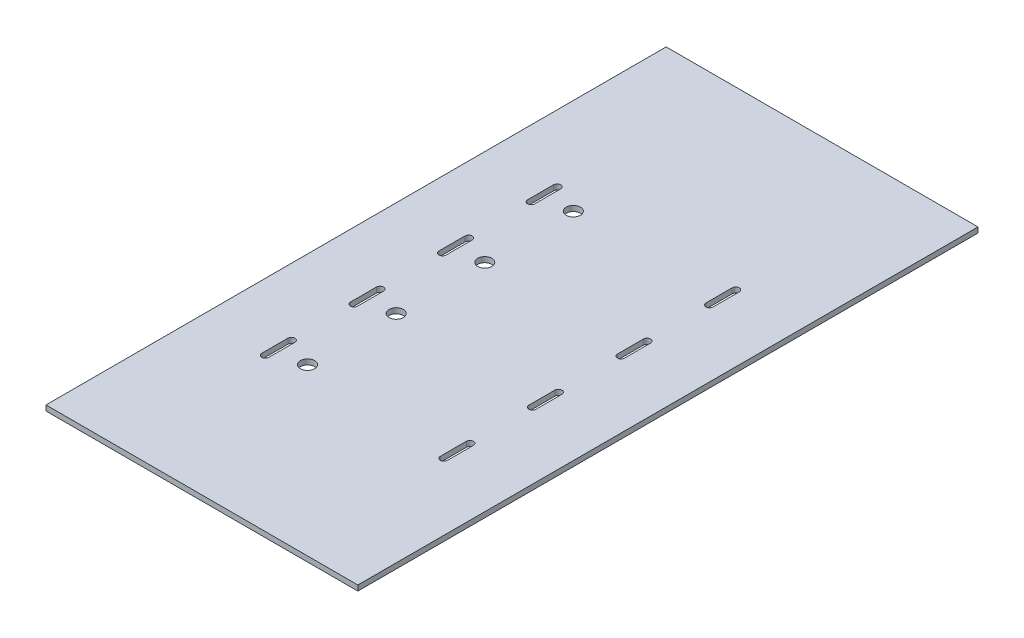
SolidWorks part; units mm, degrees
ref_plane "Front Plane" through (0, 0, 0) normal (0, 0, 1) x (1, 0, 0)
ref_plane "Top Plane" through (0, 0, 0) normal (0, 1, 0) x (1, 0, 0)
ref_plane "Right Plane" through (0, 0, 0) normal (1, 0, 0) x (0, 0, -1)
sketch "Sketch1" plane through (0, 0, 0) normal (0, 1, 0) x (1, 0, 0)
  line L1 (0, 0) -> (176, 0)
  line L2 (0, 0) -> (0, 350)
  line L3 (0, 350) -> (176, 350)
  line L4 (176, 0) -> (176, 350)
  dimension "D1" = 350
  dimension "D2" = 176
extrude "Boss-Extrude1" add sketch "Sketch1" along normal blind 3
sketch "Sketch2" plane through (0, 3, 0) normal (0, 1, 0) x (1, 0, 0)
  line L0 (176, 0) -> (176, 70)
  line L1 (176, 0) -> (176, 350) construction
  line L2 (176, 70) -> (88, 70)
  line L3 (176, 70) -> (176, 120)
  line L4 (176, 120) -> (176, 170)
  line L5 (176, 170) -> (176, 220)
  line L6 (176, 120) -> (88, 120)
  line L7 (176, 170) -> (88, 170)
  line L8 (176, 220) -> (88, 220)
  line L9 (88, 70) -> (88, 93.5)
  line L10 (88, 120) -> (88, 143.5)
  line L11 (88, 170) -> (88, 193.5)
  line L12 (88, 220) -> (88, 243.5)
hole_wizard "Ø4.0mm Dowel Slot1" positions "Sketch6" profile "Sketch7" size "Ø4.0" standard "ANSI Metric" slot yes end condition up to next
sketch "Sketch6" plane through (0, 0, 0) normal (0, -1, 0) x (-1, 0, 0)
  line L0 (-138.375, 84.15) -> (-138.375, 102.85) construction
  point P0 (-138.375, 93.5)
  point P7 (-37.625, 93.5)
  point P10 (-138.375, 143.5)
  point P13 (-37.625, 143.5)
  point P16 (-138.375, 193.5)
  point P19 (-37.625, 193.5)
  point P22 (-138.375, 243.5)
  point P25 (-37.625, 243.5)
  point P27 (0, 0)
  point P28 (-138.375, 193.5)
  point P30 (-66, 193.5)
  point P31 (-37.625, 193.5)
  point P33 (0, 0)
  point P34 (-138.375, 243.5)
  point P36 (0, 0)
  point P37 (-37.625, 243.5)
  point P38 (0, 0)
  point P39 (-37.625, 243.5)
  point P41 (0, 0)
  point P42 (0, 0)
  point P43 (-138.375, 143.5)
  point P45 (-66, 143.5)
  point P46 (-37.625, 143.5)
  point P48 (0, 0)
  point P49 (-110, 93.5)
  point P50 (-138.375, 93.5)
  point P52 (-66, 93.5)
  point P53 (-37.625, 93.5)
  dimension "D1" = 18.7
sketch "Sketch7" plane through (138.375, 0, -93.5) normal (1, 0, 0) x (0, 0, -1)
  line L0 (0, 0) -> (0, 3)
  line L1 (0, 3) -> (2, 3)
  line L2 (2, 3) -> (2, 0)
  line L5 (2, 0) -> (0, 0)
  line L11 (0, -6.35) -> (0, 107.95) construction
  dimension "Thru Hole Dia." = 4
  dimension "Thru Hole Depth" = 3
hole_wizard "Ø8.0mm Dowel Hole1" positions "Sketch8" profile "Sketch9" hole size "Ø8.0" standard "AS" end condition up to next
sketch "Sketch8" plane through (0, 3, 0) normal (0, 1, 0) x (1, 0, 0)
  point P0 (54.125, 93.5)
  point P3 (54.125, 143.5)
  point P6 (54.125, 193.5)
  point P9 (54.125, 243.5)
sketch "Sketch9" plane through (54.125, 3, -93.5) normal (1, 0, 0) x (0, 0, 1)
  line L0 (0, 0) -> (0, 3)
  line L1 (0, 3) -> (4, 3)
  line L2 (4, 3) -> (4, 0)
  line L5 (4, 0) -> (0, 0)
  line L11 (0, -6.35) -> (0, 107.95) construction
  dimension "Thru Hole Dia." = 8
  dimension "Thru Hole Depth" = 3
sketch "Sketch11" plane through (0, 0, 0) normal (0, -1, 0) x (-1, 0, 0)
  line L0 (-176, 350) -> (-176, 300)
  line L1 (-176, 0) -> (-176, 350) construction
  line L2 (-176, 300) -> (-88, 300)
sketch "Sketch14" plane through (0, 0, 0) normal (0, -1, 0) x (1, 0, 0)
  line L0 (49.9068, -300.32) -> (52.4947, -304.0511)
  line L1 (52.4947, -304.0511) -> (49.9068, -307.782)
  line L2 (49.9068, -307.782) -> (47.319, -311.513)
  line L3 (47.319, -311.513) -> (42.4156, -311.514)
  line L4 (42.4156, -311.514) -> (37.5122, -311.515)
  line L5 (37.5122, -311.515) -> (37.5122, -312.2245)
  line L6 (37.5122, -312.2245) -> (37.5122, -312.934)
  line L7 (37.5122, -312.934) -> (37.6262, -313.007)
  line L8 (36.814, -313.0151) -> (36.9178, -312.9503)
  line L9 (36.9178, -312.9503) -> (36.9187, -312.2086)
  line L10 (36.9187, -312.2086) -> (36.9195, -311.4669)
  line L11 (36.9195, -311.4669) -> (34.3456, -307.759)
  line L12 (34.3456, -307.759) -> (31.7716, -304.0511)
  line L13 (31.7716, -304.0511) -> (34.3595, -300.3201)
  line L14 (34.3595, -300.3201) -> (36.9473, -296.5891)
  line L15 (36.9473, -296.5891) -> (42.1332, -296.5891)
  line L16 (42.1332, -296.5891) -> (47.319, -296.5891)
  line L17 (47.319, -296.5891) -> (49.9068, -300.32)
  line L18 (35.9721, -306.857) -> (37.9137, -309.6536)
  line L19 (37.9137, -309.6536) -> (42.1332, -309.6536)
  line L20 (42.1332, -309.6536) -> (46.3526, -309.6536)
  line L21 (46.3526, -309.6536) -> (48.2943, -306.857)
  line L22 (46.5096, -298.6753) -> (46.3442, -298.4392)
  line L23 (46.3442, -298.4392) -> (42.129, -298.4438)
  line L24 (42.129, -298.4438) -> (37.9137, -298.4485)
  line L25 (37.9137, -298.4485) -> (35.9721, -301.2451)
  line L26 (151.2751, -299.3328) -> (144.2407, -299.3375)
  line L27 (144.2407, -299.3375) -> (143.662, -300.0043)
  line L28 (143.662, -300.0043) -> (143.0832, -300.671)
  line L29 (143.0832, -300.671) -> (143.0825, -302.0323)
  line L30 (143.0825, -302.0323) -> (143.0818, -303.3936)
  line L31 (143.0818, -303.3936) -> (143.6694, -304.074)
  line L32 (143.6694, -304.074) -> (144.257, -304.7544)
  line L33 (144.257, -304.7544) -> (149.8247, -304.7546)
  line L34 (149.8247, -304.7546) -> (155.3924, -304.7548)
  line L35 (155.3924, -304.7548) -> (156.858, -306.452)
  line L36 (156.858, -306.452) -> (158.3236, -308.1492)
  line L37 (158.3236, -308.1492) -> (158.3236, -310.1795)
  line L38 (158.3236, -310.1795) -> (158.3236, -312.2098)
  line L39 (158.3236, -312.2098) -> (156.8568, -313.9089)
  line L40 (156.8568, -313.9089) -> (155.3901, -315.6081)
  line L41 (155.3901, -315.6081) -> (148.6478, -315.6035)
  line L42 (148.6478, -315.6035) -> (141.9056, -315.5988)
  line L43 (141.9056, -315.5988) -> (141.3264, -314.2576)
  line L44 (147.7806, -312.8848) -> (154.8139, -312.8841)
  line L45 (154.8139, -312.8841) -> (155.3923, -312.2134)
  line L46 (155.3923, -312.2134) -> (155.9707, -311.5427)
  line L47 (155.9707, -311.5427) -> (155.9711, -310.1814)
  line L48 (155.9711, -310.1814) -> (155.9715, -308.82)
  line L49 (155.9715, -308.82) -> (155.3846, -308.1395)
  line L50 (155.3846, -308.1395) -> (154.7977, -307.4589)
  line L51 (154.7977, -307.4589) -> (149.23, -307.4589)
  line L52 (149.23, -307.4589) -> (143.6624, -307.4589)
  line L53 (143.6624, -307.4589) -> (142.1956, -305.7597)
  line L54 (142.1956, -305.7597) -> (140.7288, -304.0604)
  line L55 (140.7288, -304.0604) -> (140.7288, -302.0378)
  line L56 (140.7288, -302.0378) -> (140.7288, -300.0151)
  line L57 (140.7288, -300.0151) -> (140.8538, -299.8668)
  line L58 (142.3216, -298.1627) -> (143.6644, -296.6068)
  line L59 (143.6644, -296.6068) -> (150.4059, -296.6064)
  line L60 (150.4059, -296.6064) -> (157.1475, -296.606)
  line L61 (157.1475, -296.606) -> (157.7189, -297.9306)
  line L62 (136.946, -298.305) -> (138.4135, -300.0043)
  line L63 (138.4135, -300.0043) -> (138.4137, -304.0713)
  line L64 (138.4137, -304.0713) -> (138.4139, -308.1383)
  line L65 (138.4139, -308.1383) -> (136.9478, -309.8359)
  line L66 (136.9478, -309.8359) -> (135.4818, -311.5335)
  line L67 (135.4818, -311.5335) -> (130.7904, -311.5335)
  line L68 (130.7904, -311.5335) -> (126.099, -311.5335)
  line L69 (126.099, -311.5335) -> (124.6351, -309.838)
  line L70 (124.6351, -309.838) -> (123.1712, -308.1426)
  line L71 (123.1712, -308.1426) -> (123.1712, -307.1257)
  line L72 (123.1712, -307.1257) -> (123.1712, -306.1087)
  line L73 (123.1712, -306.1087) -> (124.6351, -304.4131)
  line L74 (124.6351, -304.4131) -> (126.0988, -302.7176)
  line L75 (126.0988, -302.7176) -> (130.4968, -302.7176)
  line L76 (130.4968, -302.7176) -> (134.8947, -302.7176)
  line L77 (134.8947, -302.7176) -> (134.8947, -304.0696)
  line L78 (134.8947, -304.0696) -> (134.8947, -305.4216)
  line L79 (134.8947, -305.4216) -> (130.7948, -305.4216)
  line L80 (130.7948, -305.4216) -> (126.6948, -305.4216)
  line L81 (126.6948, -305.4216) -> (126.109, -306.1002)
  line L82 (126.109, -306.1002) -> (125.5232, -306.7788)
  line L83 (125.5232, -306.7788) -> (125.5232, -307.1253)
  line L84 (125.5232, -307.1253) -> (125.5232, -307.4718)
  line L85 (125.5232, -307.4718) -> (126.1084, -308.1506)
  line L86 (126.1084, -308.1506) -> (126.6935, -308.8294)
  line L87 (126.6935, -308.8294) -> (130.7902, -308.8294)
  line L88 (130.7902, -308.8294) -> (134.887, -308.8294)
  line L89 (134.887, -308.8294) -> (135.4742, -308.1488)
  line L90 (135.4742, -308.1488) -> (136.0613, -307.4681)
  line L91 (136.0613, -307.4681) -> (136.0609, -304.0696)
  line L92 (136.0609, -304.0696) -> (136.0604, -300.671)
  line L93 (136.0604, -300.671) -> (135.4822, -300.0004)
  line L94 (135.4822, -300.0004) -> (134.904, -299.3299)
  line L95 (134.904, -299.3299) -> (129.628, -299.3291)
  line L96 (124.9416, -297.9345) -> (125.5139, -296.6065)
  line L97 (125.5139, -296.6065) -> (130.4962, -296.6061)
  line L98 (130.4962, -296.6061) -> (135.4784, -296.6057)
  line L99 (135.4784, -296.6057) -> (136.946, -298.305)
  line L100 (119.3512, -298.305) -> (120.8187, -300.0043)
  line L101 (120.8187, -300.0043) -> (120.8189, -304.0713)
  line L102 (120.8189, -304.0713) -> (120.8191, -308.1383)
  line L103 (120.8191, -308.1383) -> (119.353, -309.8359)
  line L104 (119.353, -309.8359) -> (117.887, -311.5335)
  line L105 (117.887, -311.5335) -> (112.3175, -311.5335)
  line L106 (112.3175, -311.5335) -> (106.748, -311.5335)
  line L107 (106.748, -311.5335) -> (106.4543, -310.8528)
  line L108 (105.8723, -309.5054) -> (105.584, -308.8387)
  line L109 (105.584, -308.8387) -> (111.442, -308.8294)
  line L110 (111.442, -308.8294) -> (117.3001, -308.8202)
  line L111 (117.3001, -308.8202) -> (117.8834, -308.1442)
  line L112 (117.8834, -308.1442) -> (118.4668, -307.4681)
  line L113 (118.4668, -307.4681) -> (118.4663, -304.0696)
  line L114 (118.4663, -304.0696) -> (118.4658, -300.671)
  line L115 (118.4658, -300.671) -> (117.8876, -300.0004)
  line L116 (117.8876, -300.0004) -> (117.3094, -299.3299)
  line L117 (117.3094, -299.3299) -> (111.4522, -299.3291)
  line L118 (106.172, -297.9438) -> (106.7494, -296.6057)
  line L119 (106.7494, -296.6057) -> (112.3166, -296.6057)
  line L120 (112.3166, -296.6057) -> (117.8838, -296.6057)
  line L121 (117.8838, -296.6057) -> (119.3512, -298.305)
  line L122 (101.7754, -298.3048) -> (103.2426, -300.0039)
  line L123 (103.2426, -300.0039) -> (103.2426, -305.7687)
  line L124 (103.2426, -305.7687) -> (103.2426, -311.5335)
  line L125 (103.2426, -311.5335) -> (102.0666, -311.5335)
  line L126 (102.0666, -311.5335) -> (100.8905, -311.5335)
  line L127 (100.8905, -311.5335) -> (100.8905, -306.1069)
  line L128 (100.8905, -306.1069) -> (100.8905, -300.6803)
  line L129 (100.8905, -300.6803) -> (100.3054, -300.0042)
  line L130 (100.3054, -300.0042) -> (99.7203, -299.3282)
  line L131 (99.7203, -299.3282) -> (95.6154, -299.3328)
  line L132 (95.6154, -299.3328) -> (91.5104, -299.3375)
  line L133 (91.5104, -299.3375) -> (90.9321, -300.0043)
  line L134 (90.9321, -300.0043) -> (90.3538, -300.671)
  line L135 (90.3538, -300.671) -> (90.353, -306.1022)
  line L136 (90.353, -306.1022) -> (90.3521, -311.5335)
  line L137 (90.3521, -311.5335) -> (89.1761, -311.5335)
  line L138 (89.1761, -311.5335) -> (88, -311.5335)
  line L139 (88, -311.5335) -> (88, -305.7667)
  line L140 (88, -305.7667) -> (88, -300)
  line L141 (88, -300) -> (89.4656, -298.3028)
  line L142 (89.4656, -298.3028) -> (90.9313, -296.6057)
  line L143 (90.9313, -296.6057) -> (95.6197, -296.6057)
  line L144 (95.6197, -296.6057) -> (100.3081, -296.6057)
  line L145 (100.3081, -296.6057) -> (101.7754, -298.3048)
  line L146 (85.6664, -302.372) -> (85.6664, -308.1383)
  line L147 (85.6664, -308.1383) -> (84.2003, -309.8359)
  line L148 (84.2003, -309.8359) -> (82.7342, -311.5336)
  line L149 (82.7342, -311.5336) -> (78.9209, -311.5289)
  line L150 (78.9209, -311.5289) -> (75.1076, -311.5242)
  line L151 (75.1076, -311.5242) -> (74.5278, -310.1815)
  line L152 (74.5278, -310.1815) -> (73.9479, -308.8387)
  line L153 (73.9479, -308.8387) -> (78.0476, -308.8294)
  line L154 (78.0476, -308.8294) -> (82.1474, -308.8202)
  line L155 (82.1474, -308.8202) -> (82.7307, -308.1442)
  line L156 (82.7307, -308.1442) -> (83.3141, -307.4681)
  line L157 (83.3141, -307.4681) -> (83.3141, -302.0369)
  line L158 (83.3141, -302.0369) -> (83.3141, -296.6057)
  line L159 (83.3141, -296.6057) -> (84.4901, -296.6057)
  line L160 (84.4901, -296.6057) -> (85.6662, -296.6057)
  line L161 (85.6662, -296.6057) -> (85.6664, -302.372)
  line L162 (71.6091, -306.1069) -> (71.6091, -315.6081)
  line L163 (71.6091, -315.6081) -> (64.4554, -315.6076)
  line L164 (64.4554, -315.6076) -> (57.3017, -315.6071)
  line L165 (57.3017, -315.6071) -> (55.959, -314.0512)
  line L166 (54.4912, -312.347) -> (54.3662, -312.1986)
  line L167 (54.3662, -312.1986) -> (54.3662, -310.1757)
  line L168 (54.3662, -310.1757) -> (54.3662, -308.1528)
  line L169 (54.3662, -308.1528) -> (55.1533, -307.2416)
  line L170 (54.9774, -305.1759) -> (54.0143, -304.0609)
  line L171 (54.0143, -304.0609) -> (54.0143, -302.038)
  line L172 (54.0143, -302.038) -> (54.0143, -300.0151)
  line L173 (54.0143, -300.0151) -> (54.1393, -299.8668)
  line L174 (55.6071, -298.1626) -> (56.9498, -296.6067)
  line L175 (56.9498, -296.6067) -> (64.2794, -296.6062)
  line L176 (64.2794, -296.6062) -> (71.6091, -296.6057)
  line L177 (71.6091, -296.6057) -> (71.6091, -306.1069)
  line L178 (56.9531, -300.0074) -> (56.3664, -300.6865)
  line L179 (56.3664, -300.6865) -> (56.3664, -302.0415)
  line L180 (56.3664, -302.0415) -> (56.3664, -303.3966)
  line L181 (56.3664, -303.3966) -> (56.9531, -304.0757)
  line L182 (56.9531, -304.0757) -> (57.5397, -304.7548)
  line L183 (57.5397, -304.7548) -> (62.8149, -304.7548)
  line L184 (62.8149, -304.7548) -> (68.0901, -304.7548)
  line L185 (68.0901, -304.7548) -> (68.0901, -306.1161)
  line L186 (68.0901, -306.1161) -> (68.0901, -307.4774)
  line L187 (68.0901, -307.4774) -> (62.9908, -307.4774)
  line L188 (62.9908, -307.4774) -> (57.8915, -307.4774)
  line L189 (57.8915, -307.4774) -> (57.3049, -308.1546)
  line L190 (57.3049, -308.1546) -> (56.7183, -308.8317)
  line L191 (56.7183, -308.8317) -> (56.7183, -310.1815)
  line L192 (56.7183, -310.1815) -> (56.7183, -311.5312)
  line L193 (56.7183, -311.5312) -> (57.3049, -312.2084)
  line L194 (57.3049, -312.2084) -> (57.8915, -312.8855)
  line L195 (57.8915, -312.8855) -> (63.5742, -312.8855)
  line L196 (63.5742, -312.8855) -> (69.2569, -312.8855)
  line L197 (69.2569, -312.8855) -> (69.2569, -306.1069)
  line L198 (69.2569, -306.1069) -> (69.2569, -299.3282)
  line L199 (69.2569, -299.3282) -> (63.3983, -299.3282)
  line L200 (63.3983, -299.3282) -> (57.5397, -299.3282)
  line L201 (57.5397, -299.3282) -> (56.9531, -300.0074)
  line L202 (26.4178, -298.3005) -> (27.8814, -299.9954)
  line L203 (27.8814, -299.9954) -> (27.8814, -304.4124)
  line L204 (27.8814, -304.4124) -> (27.8814, -308.8294)
  line L205 (27.8814, -308.8294) -> (29.0574, -308.8294)
  line L206 (29.0574, -308.8294) -> (30.2335, -308.8294)
  line L207 (30.2335, -308.8294) -> (30.2335, -310.1815)
  line L208 (30.2335, -310.1815) -> (30.2335, -311.5335)
  line L209 (30.2335, -311.5335) -> (29.0576, -311.5335)
  line L210 (29.0576, -311.5335) -> (27.8816, -311.5335)
  line L211 (27.8816, -311.5335) -> (27.8769, -312.896)
  line L212 (27.8769, -312.896) -> (27.8721, -314.2585)
  line L213 (27.8721, -314.2585) -> (26.7146, -314.9292)
  line L214 (26.7146, -314.9292) -> (25.557, -315.5999)
  line L215 (25.557, -315.5999) -> (25.5477, -313.5713)
  line L216 (25.5477, -313.5713) -> (25.5385, -311.5427)
  line L217 (25.5385, -311.5427) -> (22.0242, -311.5381)
  line L218 (22.0242, -311.5381) -> (18.5098, -311.5334)
  line L219 (18.5098, -311.5334) -> (18.5098, -310.1815)
  line L220 (18.5098, -310.1815) -> (18.5098, -308.8295)
  line L221 (18.5098, -308.8295) -> (22.0242, -308.8248)
  line L222 (22.0242, -308.8248) -> (25.5385, -308.8202)
  line L223 (25.5385, -308.8202) -> (25.5432, -304.7539)
  line L224 (25.5432, -304.7539) -> (25.5478, -300.6876)
  line L225 (25.5478, -300.6876) -> (24.9616, -300.0079)
  line L226 (24.9616, -300.0079) -> (24.3754, -299.3282)
  line L227 (24.3754, -299.3282) -> (21.4406, -299.3282)
  line L228 (19.6593, -296.6566) -> (19.6826, -296.6057)
  line L229 (19.6826, -296.6057) -> (22.3184, -296.6057)
  line L230 (22.3184, -296.6057) -> (24.9542, -296.6057)
  line L231 (24.9542, -296.6057) -> (26.4178, -298.3005)
  line L232 (38.4619, -314.7705) -> (38.6238, -314.9331)
  line L233 (38.6238, -314.9331) -> (38.5171, -315.0233)
  line L234 (36.0571, -314.7769) -> (36.2133, -314.624)
  line L235 (36.2133, -314.624) -> (36.3118, -314.7042)
  line L236 (39.3537, -315.6622) -> (39.5153, -315.8246)
  line L237 (39.5153, -315.8246) -> (39.3981, -315.9309)
  line L238 (35.0221, -315.8873) -> (34.9861, -315.8471)
  line L239 (34.9861, -315.8471) -> (35.1462, -315.687)
  line L240 (35.1462, -315.687) -> (35.3064, -315.5268)
  line L241 (35.3064, -315.5268) -> (35.4154, -315.6216)
  line L242 (39.042, -315.6298) -> (39.192, -315.4998)
  line L243 (39.192, -315.4998) -> (39.3537, -315.6622)
  line L244 (40.1788, -316.4874) -> (40.335, -316.6444)
  line L245 (40.335, -316.6444) -> (40.2803, -316.7024)
  line L246 (34.1888, -316.7209) -> (34.1529, -316.6808)
  line L247 (34.1529, -316.6808) -> (34.3088, -316.5241)
  spline S0 degree 3 poles (37.6262, -313.007) (37.8326, -313.1391) (37.9752, -313.396) (37.9752, -313.6356) knots 0 0 0 0 1 1 1 1
  spline S1 degree 3 poles (37.9752, -313.6356) (37.9752, -314.1241) (37.4826, -314.4928) (37.0184, -314.3518) knots 0 0 0 0 1 1 1 1
  spline S2 degree 3 poles (37.0184, -314.3518) (36.7021, -314.2557) (36.475, -313.9565) (36.475, -313.6359) knots 0 0 0 0 1 1 1 1
  spline S3 degree 3 poles (36.475, -313.6359) (36.475, -313.4005) (36.6189, -313.137) (36.814, -313.0151) knots 0 0 0 0 1 1 1 1
  spline S4 degree 3 poles (35.9721, -301.2451) (34.9042, -302.7833) (34.0305, -304.046) (34.0305, -304.0511) knots 0 0 0 0 1 1 1 1
  spline S5 degree 3 poles (34.0305, -304.0511) (34.0305, -304.0561) (34.9043, -305.3188) (35.9721, -306.857) knots 0 0 0 0 1 1 1 1
  spline S6 degree 3 poles (48.2943, -306.857) (49.3622, -305.3188) (50.2328, -304.0517) (50.2289, -304.0412) knots 0 0 0 0 1 1 1 1
  spline S7 degree 3 poles (50.2289, -304.0412) (50.2229, -304.0251) (47.0142, -299.3958) (46.5096, -298.6753) knots 0 0 0 0 1 1 1 1
  spline S8 degree 3 poles (45.5966, -302.3034) (46.003, -302.3678) (46.3168, -302.5208) (46.5936, -302.7896) knots 0 0 0 0 1 1 1 1
  spline S9 degree 3 poles (46.5936, -302.7896) (46.8322, -303.0213) (46.993, -303.2998) (47.0729, -303.6195) knots 0 0 0 0 1 1 1 1
  spline S10 degree 3 poles (47.0729, -303.6195) (47.1047, -303.7471) (47.1136, -303.8368) (47.1136, -304.0325) knots 0 0 0 0 1 1 1 1
  spline S11 degree 3 poles (47.1136, -304.0325) (47.1136, -304.404) (47.0337, -304.6804) (46.8377, -304.9874) knots 0 0 0 0 1 1 1 1
  spline S12 degree 3 poles (46.8377, -304.9874) (46.7424, -305.1366) (46.5125, -305.3698) (46.3616, -305.4702) knots 0 0 0 0 1 1 1 1
  spline S13 degree 3 poles (46.3616, -305.4702) (46.0507, -305.6771) (45.7648, -305.7625) (45.3836, -305.7625) knots 0 0 0 0 1 1 1 1
  spline S14 degree 3 poles (45.3836, -305.7625) (45.0121, -305.7625) (44.7357, -305.6827) (44.4287, -305.4867) knots 0 0 0 0 1 1 1 1
  spline S15 degree 3 poles (44.4287, -305.4867) (44.2795, -305.3914) (44.0463, -305.1615) (43.9459, -305.0106) knots 0 0 0 0 1 1 1 1
  spline S16 degree 3 poles (43.9459, -305.0106) (43.739, -304.6997) (43.6535, -304.4138) (43.6535, -304.0325) knots 0 0 0 0 1 1 1 1
  spline S17 degree 3 poles (43.6535, -304.0325) (43.6535, -303.8368) (43.6624, -303.7471) (43.6943, -303.6195) knots 0 0 0 0 1 1 1 1
  spline S18 degree 3 poles (43.6943, -303.6195) (43.7741, -303.2998) (43.9349, -303.0213) (44.1735, -302.7896) knots 0 0 0 0 1 1 1 1
  spline S19 degree 3 poles (44.1735, -302.7896) (44.4997, -302.4728) (44.87, -302.3162) (45.328, -302.3015) knots 0 0 0 0 1 1 1 1
  spline S20 degree 3 poles (45.328, -302.3015) (45.4451, -302.2977) (45.566, -302.2986) (45.5966, -302.3034) knots 0 0 0 0 1 1 1 1
  spline S21 degree 3 poles (39.1143, -302.3034) (39.5208, -302.3678) (39.8345, -302.5208) (40.1113, -302.7896) knots 0 0 0 0 1 1 1 1
  spline S22 degree 3 poles (40.1113, -302.7896) (40.3499, -303.0213) (40.5107, -303.2998) (40.5906, -303.6195) knots 0 0 0 0 1 1 1 1
  spline S23 degree 3 poles (40.5906, -303.6195) (40.6224, -303.7471) (40.6313, -303.8368) (40.6313, -304.0325) knots 0 0 0 0 1 1 1 1
  spline S24 degree 3 poles (40.6313, -304.0325) (40.6313, -304.404) (40.5514, -304.6804) (40.3554, -304.9874) knots 0 0 0 0 1 1 1 1
  spline S25 degree 3 poles (40.3554, -304.9874) (40.2601, -305.1366) (40.0302, -305.3698) (39.8793, -305.4702) knots 0 0 0 0 1 1 1 1
  spline S26 degree 3 poles (39.8793, -305.4702) (39.5684, -305.6771) (39.2825, -305.7625) (38.9013, -305.7625) knots 0 0 0 0 1 1 1 1
  spline S27 degree 3 poles (38.9013, -305.7625) (38.5195, -305.7625) (38.2345, -305.6772) (37.9216, -305.4692) knots 0 0 0 0 1 1 1 1
  spline S28 degree 3 poles (37.9216, -305.4692) (37.7744, -305.3714) (37.5401, -305.1325) (37.4442, -304.9827) knots 0 0 0 0 1 1 1 1
  spline S29 degree 3 poles (37.4442, -304.9827) (37.2515, -304.6813) (37.1713, -304.4022) (37.1713, -304.0325) knots 0 0 0 0 1 1 1 1
  spline S30 degree 3 poles (37.1713, -304.0325) (37.1713, -303.8368) (37.1801, -303.7471) (37.212, -303.6195) knots 0 0 0 0 1 1 1 1
  spline S31 degree 3 poles (37.212, -303.6195) (37.2918, -303.2998) (37.4526, -303.0213) (37.6912, -302.7896) knots 0 0 0 0 1 1 1 1
  spline S32 degree 3 poles (37.6912, -302.7896) (38.0174, -302.4728) (38.3877, -302.3162) (38.8457, -302.3015) knots 0 0 0 0 1 1 1 1
  spline S33 degree 3 poles (38.8457, -302.3015) (38.9629, -302.2977) (39.0837, -302.2986) (39.1143, -302.3034) knots 0 0 0 0 1 1 1 1
  spline S34 degree 3 poles (157.7189, -297.9306) (158.0332, -298.6591) (158.2946, -299.2716) (158.2998, -299.2917) knots 0 0 0 0 1 1 1 1
  spline S35 degree 3 poles (158.2998, -299.2917) (158.3093, -299.328) (158.2647, -299.3282) (151.2751, -299.3328) knots 0 0 0 0 1 1 1 1
  spline S36 degree 3 poles (141.3264, -314.2576) (141.0079, -313.52) (140.7473, -312.9095) (140.7473, -312.901) knots 0 0 0 0 1 1 1 1
  spline S37 degree 3 poles (140.7473, -312.901) (140.7473, -312.8925) (143.9123, -312.8852) (147.7806, -312.8848) knots 0 0 0 0 1 1 1 1
  spline S38 degree 3 poles (140.8538, -299.8668) (140.9226, -299.7852) (141.5831, -299.0184) (142.3216, -298.1627) knots 0 0 0 0 1 1 1 1
  spline S39 degree 3 poles (129.628, -299.3291) (124.5864, -299.3283) (124.3524, -299.3268) (124.3606, -299.2954) knots 0 0 0 0 1 1 1 1
  spline S40 degree 3 poles (124.3606, -299.2954) (124.3654, -299.2773) (124.6268, -298.6649) (124.9416, -297.9345) knots 0 0 0 0 1 1 1 1
  spline S41 degree 3 poles (106.4543, -310.8528) (106.2928, -310.4785) (106.0309, -309.8722) (105.8723, -309.5054) knots 0 0 0 0 1 1 1 1
  spline S42 degree 3 poles (111.4522, -299.3291) (106.7793, -299.3284) (105.5949, -299.3236) (105.5948, -299.3051) knots 0 0 0 0 1 1 1 1
  spline S43 degree 3 poles (105.5948, -299.3051) (105.5948, -299.2924) (105.8545, -298.6798) (106.172, -297.9438) knots 0 0 0 0 1 1 1 1
  spline S44 degree 3 poles (55.959, -314.0512) (55.2204, -313.1955) (54.5599, -312.4286) (54.4912, -312.347) knots 0 0 0 0 1 1 1 1
  spline S45 degree 3 poles (55.1533, -307.2416) (55.5862, -306.7405) (55.9404, -306.3216) (55.9404, -306.3106) knots 0 0 0 0 1 1 1 1
  spline S46 degree 3 poles (55.9404, -306.3106) (55.9404, -306.2997) (55.507, -305.7891) (54.9774, -305.1759) knots 0 0 0 0 1 1 1 1
  spline S47 degree 3 poles (54.1393, -299.8668) (54.208, -299.7852) (54.8685, -299.0184) (55.6071, -298.1626) knots 0 0 0 0 1 1 1 1
  spline S48 degree 3 poles (21.4406, -299.3282) (19.1003, -299.3282) (18.5077, -299.3236) (18.5151, -299.3051) knots 0 0 0 0 1 1 1 1
  spline S49 degree 3 poles (18.5151, -299.3051) (18.5311, -299.2648) (19.6349, -296.7099) (19.6593, -296.6566) knots 0 0 0 0 1 1 1 1
  spline S50 degree 3 poles (38.5171, -315.0233) (38.2916, -315.214) (38.014, -315.3578) (37.7197, -315.4363) knots 0 0 0 0 1 1 1 1
  spline S51 degree 3 poles (37.7197, -315.4363) (37.5619, -315.4784) (37.5038, -315.4843) (37.2437, -315.4843) knots 0 0 0 0 1 1 1 1
  spline S52 degree 3 poles (37.2437, -315.4843) (36.9835, -315.4843) (36.9254, -315.4784) (36.7676, -315.4363) knots 0 0 0 0 1 1 1 1
  spline S53 degree 3 poles (36.7676, -315.4363) (36.5566, -315.38) (36.3188, -315.2726) (36.1452, -315.1552) knots 0 0 0 0 1 1 1 1
  spline S54 degree 3 poles (36.1452, -315.1552) (36.0115, -315.0649) (35.9009, -314.9697) (35.9009, -314.945) knots 0 0 0 0 1 1 1 1
  spline S55 degree 3 poles (35.9009, -314.945) (35.9009, -314.9366) (35.9712, -314.861) (36.0571, -314.7769) knots 0 0 0 0 1 1 1 1
  spline S56 degree 3 poles (36.3118, -314.7042) (36.8579, -315.1486) (37.6828, -315.1393) (38.2015, -314.6828) knots 0 0 0 0 1 1 1 1
  spline S57 degree 3 poles (38.2015, -314.6828) (38.2482, -314.6416) (38.2896, -314.6079) (38.2933, -314.6079) knots 0 0 0 0 1 1 1 1
  spline S58 degree 3 poles (38.2933, -314.6079) (38.2971, -314.6079) (38.3729, -314.6811) (38.4619, -314.7705) knots 0 0 0 0 1 1 1 1
  spline S59 degree 3 poles (39.3981, -315.9309) (38.8794, -316.4016) (38.265, -316.6771) (37.5585, -316.756) knots 0 0 0 0 1 1 1 1
  spline S60 degree 3 poles (37.5585, -316.756) (36.7288, -316.8486) (35.8597, -316.5842) (35.1898, -316.0353) knots 0 0 0 0 1 1 1 1
  spline S61 degree 3 poles (35.1898, -316.0353) (35.1174, -315.9761) (35.042, -315.9094) (35.0221, -315.8873) knots 0 0 0 0 1 1 1 1
  spline S62 degree 3 poles (35.4154, -315.6216) (35.689, -315.8596) (36.0445, -316.0655) (36.3639, -316.171) knots 0 0 0 0 1 1 1 1
  spline S63 degree 3 poles (36.3639, -316.171) (36.666, -316.2707) (36.8654, -316.3004) (37.2344, -316.3004) knots 0 0 0 0 1 1 1 1
  spline S64 degree 3 poles (37.2344, -316.3004) (37.5201, -316.3004) (37.6094, -316.2934) (37.7715, -316.2586) knots 0 0 0 0 1 1 1 1
  spline S65 degree 3 poles (37.7715, -316.2586) (38.267, -316.1522) (38.6684, -315.9536) (39.042, -315.6298) knots 0 0 0 0 1 1 1 1
  spline S66 degree 3 poles (40.2803, -316.7024) (40.2502, -316.7343) (40.1463, -316.8269) (40.0496, -316.9083) knots 0 0 0 0 1 1 1 1
  spline S67 degree 3 poles (40.0496, -316.9083) (39.2692, -317.5644) (38.2382, -317.9416) (37.2251, -317.9416) knots 0 0 0 0 1 1 1 1
  spline S68 degree 3 poles (37.2251, -317.9416) (36.2123, -317.9416) (35.1835, -317.5653) (34.4007, -316.9086) knots 0 0 0 0 1 1 1 1
  spline S69 degree 3 poles (34.4007, -316.9086) (34.3039, -316.8274) (34.2086, -316.743) (34.1888, -316.7209) knots 0 0 0 0 1 1 1 1
  spline S70 degree 3 poles (34.3088, -316.5241) (34.3946, -316.4379) (34.4691, -316.3677) (34.4744, -316.3681) knots 0 0 0 0 1 1 1 1
  spline S71 degree 3 poles (34.4744, -316.3681) (34.4797, -316.3684) (34.5703, -316.4431) (34.6756, -316.534) knots 0 0 0 0 1 1 1 1
  spline S72 degree 3 poles (34.6756, -316.534) (35.5868, -317.3201) (36.8012, -317.6377) (37.9937, -317.4018) knots 0 0 0 0 1 1 1 1
  spline S73 degree 3 poles (37.9937, -317.4018) (38.6703, -317.268) (39.2609, -316.9775) (39.8006, -316.5131) knots 0 0 0 0 1 1 1 1
  spline S74 degree 3 poles (39.8006, -316.5131) (39.9174, -316.4126) (40.0151, -316.3304) (40.0178, -316.3304) knots 0 0 0 0 1 1 1 1
  spline S75 degree 3 poles (40.0178, -316.3304) (40.0204, -316.3304) (40.0929, -316.401) (40.1788, -316.4874) knots 0 0 0 0 1 1 1 1
extrude "Cut-Extrude1" cut sketch "Sketch14" against normal blind 0.5 contours S38 L57 L56 L55 L54 L53 L52 L51 L50 L49 L48 L47 L46 L45 L44 S37 S36 L43 L42 L41 L40 L39 L38 L37 L36 L35 L34 L33 L32 L31 L30 L29 L28 L27 L26 S35 S34 L61 L60 L59 L58 | S40 S39 L95 L94 L93 L92 L91 L90 L89 L88 L87 L86 L85 L84 L83 L82 L81 L80 L79 L78 L77 L76 L75 L74 L73 L72 L71 L70 L69 L68 L67 L66 L65 L64 L63 L62 L99 L98 L97 L96 | S43 S42 L117 L116 L115 L114 L113 L112 L111 L110 L109 L108 S41 L107 L106 L105 L104 L103 L102 L101 L100 L121 L120 L119 L118 | L145 L144 L143 L142 L141 L140 L139 L138 L137 L136 L135 L134 L133 L132 L131 L130 L129 L128 L127 L126 L125 L124 L123 L122 | L161 L160 L159 L158 L157 L156 L155 L154 L153 L152 L151 L150 L149 L148 L147 L146 | S47 L173 L172 L171 L170 S46 S45 L169 L168 L167 L166 S44 L165 L164 L163 L162 L177 L176 L175 L174 L201 L200 L199 L198 L197 L196 L195 L194 L193 L192 L191 L190 L189 L188 L187 L186 L185 L184 L183 L182 L181 L180 L179 L178 | S3 S2 S1 S0 L7 L6 L5 L4 L3 L2 L1 L0 L17 L16 L15 L14 L13 L12 L11 L10 L9 L8 S7 S6 L21 L20 L19 L18 S5 S4 L25 L24 L23 L22 | S20 S19 S18 S17 S16 S15 S14 S13 S12 S11 S10 S9 S8 | S33 S32 S31 S30 S29 S28 S27 S26 S25 S24 S23 S22 S21 | S49 S48 L227 L226 L225 L224 L223 L222 L221 L220 L219 L218 L217 L216 L215 L214 L213 L212 L211 L210 L209 L208 L207 L206 L205 L204 L203 L202 L231 L230 L229 L228 | S75 S74 S73 S72 S71 S70 L247 L246 S69 S68 S67 S66 L245 L244 | S65 S64 S63 S62 L241 L240 L239 L238 S61 S60 S59 L237 L236 L243 L242 | S58 S57 S56 L235 L234 S55 S54 S53 S52 S51 S50 L233 L232 region at (50.9763, 0, -302.3412) region at (149.529, 0, -306.1002) region at (131.3483, 0, -304.2967) region at (119.9235, 0, -299.294) region at (102.3475, 0, -299.2938) region at (85.4766, 0, -305.2551) region at (63.2832, 0, -306.0633) region at (26.9806, 0, -299.2938) region at (37.2563, 0, -315.1056) region at (39.4011, 0, -315.7766) region at (40.2116, 0, -316.611) region at (45.3836, 0, -304.0326) region at (38.9013, 0, -304.0325)
